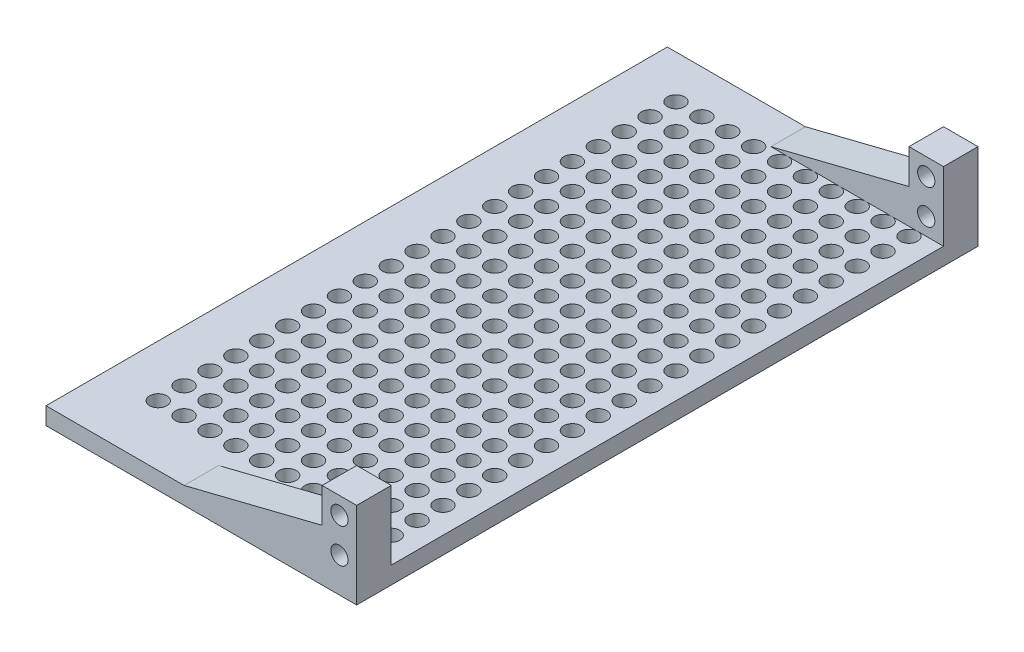
SolidWorks part; units mm, degrees
ref_plane "Plan de face" through (0, 0, 0) normal (0, 0, 1) x (1, 0, 0)
ref_plane "Plan de dessus" through (0, 0, 0) normal (0, 1, 0) x (1, 0, 0)
ref_plane "Plan de droite" through (0, 0, 0) normal (1, 0, 0) x (0, 0, -1)
sketch "Esquisse1" plane through (0, 0, 0) normal (0, 0, 1) x (1, 0, 0)
  line L1 (-45, -2.5) -> (45, -2.5)
  line L2 (-45, -2.5) -> (-45, 2.5)
  line L3 (-45, 2.5) -> (45, 2.5)
  line L4 (45, -2.5) -> (45, 2.5)
  line L5 (-45, -2.5) -> (45, 2.5) construction
  line L6 (-45, 2.5) -> (45, -2.5) construction
  point P0 (0, 0)
  dimension "D1" = 90
  dimension "D2" = 5
extrude "Boss.-Extru.1" add sketch "Esquisse1" along normal blind 180
sketch "Esquisse2" plane through (0, 2.5, 0) normal (0, 1, 0) x (1, 0, 0)
  line L0 (45, -90) -> (-45, -90) construction
  line L1 (45, 0) -> (35, 0)
  line L2 (45, 0) -> (45, -10)
  line L3 (45, -10) -> (35, -10)
  line L4 (35, 0) -> (35, -10)
  line L5 (45, -180) -> (35, -180)
  line L6 (45, -180) -> (45, -170)
  line L7 (45, -170) -> (35, -170)
  line L8 (35, -180) -> (35, -170)
  line L9 (45, -180) -> (45, 0) construction
  line L10 (-45, -180) -> (-45, 0) construction
  dimension "D1" = 10
  dimension "D2" = 10
  dimension "D3" = 10
  dimension "D4" = 10
extrude "Boss.-Extru.2" add sketch "Esquisse2" along normal blind 20
sketch "Esquisse3" plane through (0, 0, 180) normal (0, 0, 1) x (1, 0, 0)
  line L0 (35, 22.5) -> (45, 2.5) construction
  line L1 (45, 2.5) -> (35, 2.5) construction
  line L2 (35, 2.5) -> (45, 22.5) construction
  line L3 (45, 22.5) -> (40, 22.5) construction
  line L4 (35, 22.5) -> (45, 22.5) construction
  line L5 (40, 22.5) -> (40, 2.5) construction
  circle A0 centre (40, 17.5) radius 2.5
  circle A1 centre (40, 7.5) radius 2.5
  point P16 (40, 12.5)
  dimension "D1" = 5
  dimension "D2" = 5
  dimension "D3" = 5
  dimension "D4" = 5
extrude "Enlèv. mat.-Extru.1" cut sketch "Esquisse3" against normal up to surface (10 mm away) up to face at (40, 12.5, 170)
sketch "Esquisse4" plane through (0, 0, 180) normal (0, 0, 1) x (1, 0, 0)
  line L0 (35, 12.5) -> (-5, 2.5)
  line L1 (35, 22.5) -> (35, 2.5) construction
  line L2 (35, 2.5) -> (-45, 2.5) construction
  line L3 (-5, 2.5) -> (35, 2.5)
  line L4 (35, 2.5) -> (35, 12.5)
extrude "Boss.-Extru.3" add sketch "Esquisse4" against normal blind 10
ref_plane "Plan1" through (0, 0, 90) normal (0, 0, 1) x (1, 0, 0)
mirror "Symétrie1" about plane through (0, 0, 90) normal (0, 0, 1) of "Enlèv. mat.-Extru.1", "Boss.-Extru.3"
sketch "Esquisse5" plane through (0, 2.5, 0) normal (0, 1, 0) x (1, 0, 0)
  line L0 (45, -170) -> (45, -10) construction
  line L1 (45, -170) -> (35, -170) construction
  circle A0 centre (37.5, -162.5) radius 2.5
  circle A1 centre (30, -162.5) radius 2.5
  circle A2 centre (22.5, -162.5) radius 2.5
  circle A3 centre (15, -162.5) radius 2.5
  circle A4 centre (7.5, -162.5) radius 2.5
  circle A5 centre (0, -162.5) radius 2.5
  circle A6 centre (-7.5, -162.5) radius 2.5
  circle A7 centre (-15, -162.5) radius 2.5
  circle A8 centre (-22.5, -162.5) radius 2.5
  circle A9 centre (-30, -162.5) radius 2.5
  circle A10 centre (30, -155) radius 2.5
  circle A11 centre (22.5, -155) radius 2.5
  circle A12 centre (15, -155) radius 2.5
  circle A13 centre (7.5, -155) radius 2.5
  circle A14 centre (0, -155) radius 2.5
  circle A15 centre (-7.5, -155) radius 2.5
  circle A16 centre (-15, -155) radius 2.5
  circle A17 centre (-22.5, -155) radius 2.5
  circle A18 centre (-30, -155) radius 2.5
  circle A19 centre (30, -147.5) radius 2.5
  circle A20 centre (22.5, -147.5) radius 2.5
  circle A21 centre (15, -147.5) radius 2.5
  circle A22 centre (7.5, -147.5) radius 2.5
  circle A23 centre (0, -147.5) radius 2.5
  circle A24 centre (-7.5, -147.5) radius 2.5
  circle A25 centre (-15, -147.5) radius 2.5
  circle A26 centre (-22.5, -147.5) radius 2.5
  circle A27 centre (-30, -147.5) radius 2.5
  circle A28 centre (30, -140) radius 2.5
  circle A29 centre (22.5, -140) radius 2.5
  circle A30 centre (15, -140) radius 2.5
  circle A31 centre (7.5, -140) radius 2.5
  circle A32 centre (0, -140) radius 2.5
  circle A33 centre (-7.5, -140) radius 2.5
  circle A34 centre (-15, -140) radius 2.5
  circle A35 centre (-22.5, -140) radius 2.5
  circle A36 centre (-30, -140) radius 2.5
  circle A37 centre (30, -132.5) radius 2.5
  circle A38 centre (22.5, -132.5) radius 2.5
  circle A39 centre (15, -132.5) radius 2.5
  circle A40 centre (7.5, -132.5) radius 2.5
  circle A41 centre (0, -132.5) radius 2.5
  circle A42 centre (-7.5, -132.5) radius 2.5
  circle A43 centre (-15, -132.5) radius 2.5
  circle A44 centre (-22.5, -132.5) radius 2.5
  circle A45 centre (-30, -132.5) radius 2.5
  circle A46 centre (30, -125) radius 2.5
  circle A47 centre (22.5, -125) radius 2.5
  circle A48 centre (15, -125) radius 2.5
  circle A49 centre (7.5, -125) radius 2.5
  circle A50 centre (0, -125) radius 2.5
  circle A51 centre (-7.5, -125) radius 2.5
  circle A52 centre (-15, -125) radius 2.5
  circle A53 centre (-22.5, -125) radius 2.5
  circle A54 centre (-30, -125) radius 2.5
  circle A55 centre (30, -117.5) radius 2.5
  circle A56 centre (22.5, -117.5) radius 2.5
  circle A57 centre (15, -117.5) radius 2.5
  circle A58 centre (7.5, -117.5) radius 2.5
  circle A59 centre (0, -117.5) radius 2.5
  circle A60 centre (-7.5, -117.5) radius 2.5
  circle A61 centre (-15, -117.5) radius 2.5
  circle A62 centre (-22.5, -117.5) radius 2.5
  circle A63 centre (-30, -117.5) radius 2.5
  circle A64 centre (30, -110) radius 2.5
  circle A65 centre (22.5, -110) radius 2.5
  circle A66 centre (15, -110) radius 2.5
  circle A67 centre (7.5, -110) radius 2.5
  circle A68 centre (0, -110) radius 2.5
  circle A69 centre (-7.5, -110) radius 2.5
  circle A70 centre (-15, -110) radius 2.5
  circle A71 centre (-22.5, -110) radius 2.5
  circle A72 centre (-30, -110) radius 2.5
  circle A73 centre (30, -102.5) radius 2.5
  circle A74 centre (22.5, -102.5) radius 2.5
  circle A75 centre (15, -102.5) radius 2.5
  circle A76 centre (7.5, -102.5) radius 2.5
  circle A77 centre (0, -102.5) radius 2.5
  circle A78 centre (-7.5, -102.5) radius 2.5
  circle A79 centre (-15, -102.5) radius 2.5
  circle A80 centre (-22.5, -102.5) radius 2.5
  circle A81 centre (-30, -102.5) radius 2.5
  circle A82 centre (30, -95) radius 2.5
  circle A83 centre (22.5, -95) radius 2.5
  circle A84 centre (15, -95) radius 2.5
  circle A85 centre (7.5, -95) radius 2.5
  circle A86 centre (0, -95) radius 2.5
  circle A87 centre (-7.5, -95) radius 2.5
  circle A88 centre (-15, -95) radius 2.5
  circle A89 centre (-22.5, -95) radius 2.5
  circle A90 centre (-30, -95) radius 2.5
  circle A91 centre (30, -87.5) radius 2.5
  circle A92 centre (22.5, -87.5) radius 2.5
  circle A93 centre (15, -87.5) radius 2.5
  circle A94 centre (7.5, -87.5) radius 2.5
  circle A95 centre (0, -87.5) radius 2.5
  circle A96 centre (-7.5, -87.5) radius 2.5
  circle A97 centre (-15, -87.5) radius 2.5
  circle A98 centre (-22.5, -87.5) radius 2.5
  circle A99 centre (-30, -87.5) radius 2.5
  circle A100 centre (30, -80) radius 2.5
  circle A101 centre (22.5, -80) radius 2.5
  circle A102 centre (15, -80) radius 2.5
  circle A103 centre (7.5, -80) radius 2.5
  circle A104 centre (0, -80) radius 2.5
  circle A105 centre (-7.5, -80) radius 2.5
  circle A106 centre (-15, -80) radius 2.5
  circle A107 centre (-22.5, -80) radius 2.5
  circle A108 centre (-30, -80) radius 2.5
  circle A109 centre (30, -72.5) radius 2.5
  circle A110 centre (22.5, -72.5) radius 2.5
  circle A111 centre (15, -72.5) radius 2.5
  circle A112 centre (7.5, -72.5) radius 2.5
  circle A113 centre (0, -72.5) radius 2.5
  circle A114 centre (-7.5, -72.5) radius 2.5
  circle A115 centre (-15, -72.5) radius 2.5
  circle A116 centre (-22.5, -72.5) radius 2.5
  circle A117 centre (-30, -72.5) radius 2.5
  circle A118 centre (30, -65) radius 2.5
  circle A119 centre (22.5, -65) radius 2.5
  circle A120 centre (15, -65) radius 2.5
  circle A121 centre (7.5, -65) radius 2.5
  circle A122 centre (0, -65) radius 2.5
  circle A123 centre (-7.5, -65) radius 2.5
  circle A124 centre (-15, -65) radius 2.5
  circle A125 centre (-22.5, -65) radius 2.5
  circle A126 centre (-30, -65) radius 2.5
  circle A127 centre (30, -57.5) radius 2.5
  circle A128 centre (22.5, -57.5) radius 2.5
  circle A129 centre (15, -57.5) radius 2.5
  circle A130 centre (7.5, -57.5) radius 2.5
  circle A131 centre (0, -57.5) radius 2.5
  circle A132 centre (-7.5, -57.5) radius 2.5
  circle A133 centre (-15, -57.5) radius 2.5
  circle A134 centre (-22.5, -57.5) radius 2.5
  circle A135 centre (-30, -57.5) radius 2.5
  circle A136 centre (30, -50) radius 2.5
  circle A137 centre (22.5, -50) radius 2.5
  circle A138 centre (15, -50) radius 2.5
  circle A139 centre (7.5, -50) radius 2.5
  circle A140 centre (0, -50) radius 2.5
  circle A141 centre (-7.5, -50) radius 2.5
  circle A142 centre (-15, -50) radius 2.5
  circle A143 centre (-22.5, -50) radius 2.5
  circle A144 centre (-30, -50) radius 2.5
  circle A145 centre (30, -42.5) radius 2.5
  circle A146 centre (22.5, -42.5) radius 2.5
  circle A147 centre (15, -42.5) radius 2.5
  circle A148 centre (7.5, -42.5) radius 2.5
  circle A149 centre (0, -42.5) radius 2.5
  circle A150 centre (-7.5, -42.5) radius 2.5
  circle A151 centre (-15, -42.5) radius 2.5
  circle A152 centre (-22.5, -42.5) radius 2.5
  circle A153 centre (-30, -42.5) radius 2.5
  circle A154 centre (30, -35) radius 2.5
  circle A155 centre (22.5, -35) radius 2.5
  circle A156 centre (15, -35) radius 2.5
  circle A157 centre (7.5, -35) radius 2.5
  circle A158 centre (0, -35) radius 2.5
  circle A159 centre (-7.5, -35) radius 2.5
  circle A160 centre (-15, -35) radius 2.5
  circle A161 centre (-22.5, -35) radius 2.5
  circle A162 centre (-30, -35) radius 2.5
  circle A163 centre (30, -27.5) radius 2.5
  circle A164 centre (22.5, -27.5) radius 2.5
  circle A165 centre (15, -27.5) radius 2.5
  circle A166 centre (7.5, -27.5) radius 2.5
  circle A167 centre (0, -27.5) radius 2.5
  circle A168 centre (-7.5, -27.5) radius 2.5
  circle A169 centre (-15, -27.5) radius 2.5
  circle A170 centre (-22.5, -27.5) radius 2.5
  circle A171 centre (-30, -27.5) radius 2.5
  circle A172 centre (30, -20) radius 2.5
  circle A173 centre (22.5, -20) radius 2.5
  circle A174 centre (15, -20) radius 2.5
  circle A175 centre (7.5, -20) radius 2.5
  circle A176 centre (0, -20) radius 2.5
  circle A177 centre (-7.5, -20) radius 2.5
  circle A178 centre (-15, -20) radius 2.5
  circle A179 centre (-22.5, -20) radius 2.5
  circle A180 centre (-30, -20) radius 2.5
  circle A181 centre (30, -12.5) radius 2.5
  circle A182 centre (22.5, -12.5) radius 2.5
  circle A183 centre (15, -12.5) radius 2.5
  circle A184 centre (7.5, -12.5) radius 2.5
  circle A185 centre (0, -12.5) radius 2.5
  circle A186 centre (-7.5, -12.5) radius 2.5
  circle A187 centre (-15, -12.5) radius 2.5
  circle A188 centre (-22.5, -12.5) radius 2.5
  circle A189 centre (-30, -12.5) radius 2.5
  circle A190 centre (37.5, -155) radius 2.5
  circle A191 centre (37.5, -147.5) radius 2.5
  circle A192 centre (37.5, -140) radius 2.5
  circle A193 centre (37.5, -132.5) radius 2.5
  circle A194 centre (37.5, -125) radius 2.5
  circle A195 centre (37.5, -117.5) radius 2.5
  circle A196 centre (37.5, -110) radius 2.5
  circle A197 centre (37.5, -102.5) radius 2.5
  circle A198 centre (37.5, -95) radius 2.5
  circle A199 centre (37.5, -87.5) radius 2.5
  circle A200 centre (37.5, -80) radius 2.5
  circle A201 centre (37.5, -72.5) radius 2.5
  circle A202 centre (37.5, -65) radius 2.5
  circle A203 centre (37.5, -57.5) radius 2.5
  circle A204 centre (37.5, -50) radius 2.5
  circle A205 centre (37.5, -42.5) radius 2.5
  circle A206 centre (37.5, -35) radius 2.5
  circle A207 centre (37.5, -27.5) radius 2.5
  circle A208 centre (37.5, -20) radius 2.5
  circle A209 centre (37.5, -12.5) radius 2.5
  dimension "D1" = 5
  dimension "D2" = 7.5
  dimension "D3" = 7.5
  dimension "D4" = 10
  dimension "D5" = 21
extrude "Enlèv. mat.-Extru.2" cut sketch "Esquisse5" against normal up to surface (5 mm away) up to face at (0, -2.5, 90)
